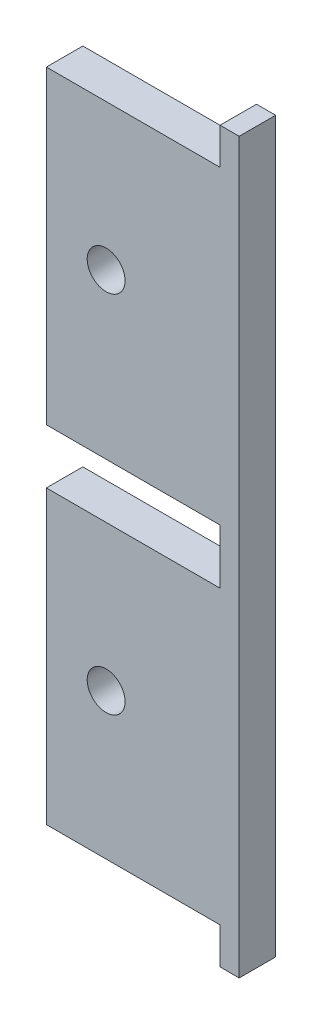
SolidWorks part; units mm, degrees
material "AISI 4130 Steel, annealed at 865C"
ref_plane "X-Y Datum" through (0, 0, 0) normal (0, 0, 1) x (1, 0, 0)
ref_plane "X-Z Datum" through (0, 0, 0) normal (0, 1, 0) x (1, 0, 0)
ref_plane "Y-Z Datum" through (0, 0, 0) normal (1, 0, 0) x (0, 0, -1)
sketch "Sketch2" plane through (0, 0, 0) normal (0, 0, 1) x (1, 0, 0)
  line L0 (34.925, 127) -> (0, 127) construction
  line L1 (0, 0) -> (40.64, 0)
  line L2 (0, 0) -> (0, 127)
  line L3 (0, 127) -> (40.64, 127)
  line L4 (40.64, 0) -> (40.64, 127)
  point P7 (17.4625, 31.75)
  point P8 (17.4625, 95.25)
  dimension "D1" = 40.64
extrude "Boss-Extrude1" add sketch "Sketch2" along normal blind 6.35
hole_wizard "M6 Clearance Hole1" positions "Sketch3" profile "Sketch4" hole size "M6" standard "ANSI Metric" end condition through all
sketch "Sketch3" plane through (0, 0, 6.35) normal (0, 0, 1) x (1, 0, 0)
  point P0 (17.4625, 31.75)
  point P3 (17.4625, 95.25)
sketch "Sketch4" plane through (17.4625, 31.75, 6.35) normal (1, 0, 0) x (0, -1, 0)
  line L0 (0, 0) -> (0, 6.35)
  line L1 (0, 6.35) -> (3.3, 6.35)
  line L2 (3.3, 6.35) -> (3.3, 0)
  line L5 (3.3, 0) -> (0, 0)
  line L11 (0, -6.35) -> (0, 107.95) construction
  dimension "Thru Hole Dia." = 6.6
  dimension "Thru Hole Depth" = 6.35
sketch "Sketch5" plane through (0, 0, 6.35) normal (0, 0, 1) x (1, 0, 0)
  line L0 (7.0505, 127) -> (7.0505, 0)
  line L1 (40.64, 127) -> (0, 127) construction
  line L2 (0, 0) -> (40.64, 0) construction
  circle A0 centre (17.4625, 95.25) radius 3.3 construction
  point P6 (14.1625, 95.25)
  line M4 (0, 127) -> (0, 0)
  line M5 (0, 0) -> (40.64, 0)
  line M7 (40.64, 127) -> (0, 127)
  dimension "D1" = 7.112
extrude "Cut-Extrude1" cut sketch "Sketch5" against normal through all and the other way through all contours L0 M7 M4 M5 region at (3.5253, 63.5, 6.35)
sketch "Sketch6" plane through (0, 0, 6.35) normal (0, 0, 1) x (1, 0, 0)
  line L0 (-3.175, 120.65) -> (38.1, 120.65)
  line L1 (38.1, 120.65) -> (38.1, 130.175)
  line L2 (38.1, 130.175) -> (-3.175, 130.175)
  line L3 (-3.175, 130.175) -> (-3.175, 120.65)
  line L4 (0, 123.825) -> (34.925, 123.825)
  line L5 (34.925, 123.825) -> (34.925, 127)
  line L6 (34.925, 127) -> (0, 127)
  line L7 (0, 127) -> (0, 123.825)
  line L8 (0, 123.825) -> (34.925, 123.825)
  line L9 (34.925, 123.825) -> (34.925, 127)
  line L10 (34.925, 127) -> (0, 127)
  line L11 (0, 127) -> (0, 123.825)
  line L12 (0, 60.325) -> (34.925, 60.325)
  line L13 (34.925, 60.325) -> (34.925, 63.5)
  line L14 (34.925, 63.5) -> (0, 63.5)
  line L15 (0, 63.5) -> (0, 60.325)
  line L16 (0, 60.325) -> (34.925, 60.325)
  line L17 (34.925, 60.325) -> (34.925, 63.5)
  line L18 (34.925, 63.5) -> (0, 63.5)
  line L19 (0, 63.5) -> (0, 60.325)
  line L20 (0, 0) -> (34.925, 0)
  line L21 (34.925, 0) -> (34.925, 3.175)
  line L22 (34.925, 3.175) -> (0, 3.175)
  line L23 (0, 3.175) -> (0, 0)
  line L24 (0, 0) -> (34.925, 0)
  line L25 (34.925, 0) -> (34.925, 3.175)
  line L26 (34.925, 3.175) -> (0, 3.175)
  line L27 (0, 3.175) -> (0, 0)
  line L28 (38.1, 66.675) -> (-3.175, 66.675)
  line L29 (-3.175, 66.675) -> (-3.175, 57.15)
  line L30 (-3.175, 57.15) -> (38.1, 57.15)
  line L31 (38.1, 57.15) -> (38.1, 66.675)
  line L32 (38.1, 6.35) -> (-3.175, 6.35)
  line L33 (-3.175, 6.35) -> (-3.175, -3.175)
  line L34 (-3.175, -3.175) -> (38.1, -3.175)
  line L35 (38.1, -3.175) -> (38.1, 6.35)
  line L36 (37.3062, 127) -> (37.3063, 0)
  line L37 (40.64, 127) -> (7.0505, 127) construction
  line L38 (7.0505, 0) -> (40.64, 0) construction
  line M19 (7.0505, 127) -> (7.0505, 0)
  line M20 (7.0505, 0) -> (40.64, 0)
  line M22 (40.64, 127) -> (7.0505, 127)
  dimension "D5" = 2.3813
  dimension "D1" = 0
  dimension "D2" = 0
  dimension "D3" = 0
  dimension "D4" = 3.175
extrude "Cut-Extrude2" cut sketch "Sketch6" against normal through all contours L36 L9 L8 L0 M22 M19 | L8 L9 M22 M19 | L36 L28 L18 L17 L16 L30 M19 | L17 L18 L16 M19 | L36 L32 L26 L25 M19 M20 | L25 L26 M19 M20 region at (23.1953, 122.4692, 6.35) region at (20.9877, 125.4125, 6.35) region at (22.1784, 66.3578, 6.35) region at (20.9878, 61.9125, 6.35) region at (23.1953, 4.5308, 6.35) region at (20.9878, 1.5875, 6.35)
